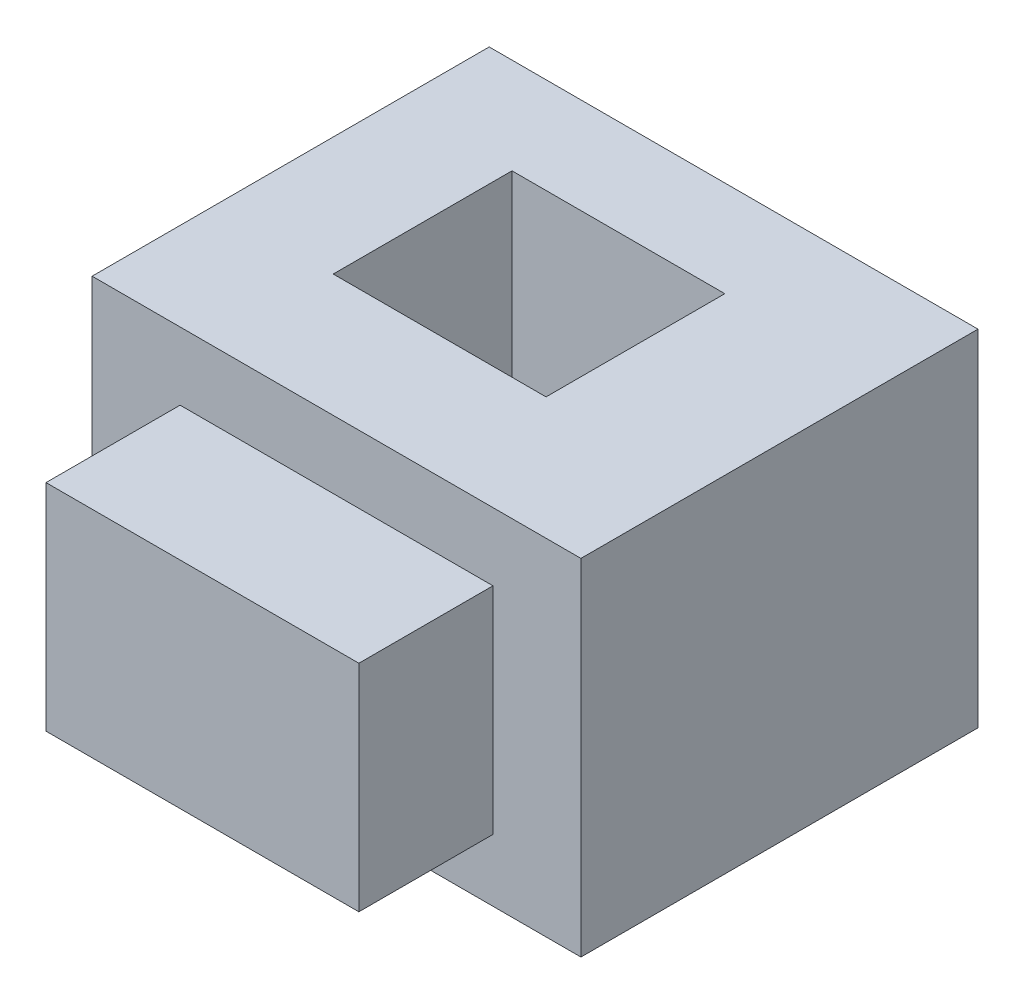
SolidWorks part; units mm, degrees
ref_plane "Front Plane" through (0, 0, 0) normal (0, 0, 1) x (1, 0, 0)
ref_plane "Top Plane" through (0, 0, 0) normal (0, 1, 0) x (1, 0, 0)
ref_plane "Right Plane" through (0, 0, 0) normal (1, 0, 0) x (0, 0, -1)
sketch "Sketch1" plane through (0, 0, 0) normal (0, 1, 0) x (1, 0, 0)
  line L1 (0, 0) -> (36.4531, 0)
  line L2 (0, 0) -> (0, 29.6127)
  line L3 (0, 29.6127) -> (36.4531, 29.6127)
  line L4 (36.4531, 0) -> (36.4531, 29.6127)
extrude "Boss-Extrude1" add sketch "Sketch1" along normal blind 25.7503
sketch "Sketch3" plane through (0, 0, 0) normal (0, 0, 1) x (1, 0, 0)
  line L1 (6.56, 20.699) -> (29.8931, 20.699)
  line L2 (6.56, 20.699) -> (6.56, 4.6431)
  line L3 (6.56, 4.6431) -> (29.8931, 4.6431)
  line L4 (29.8931, 20.699) -> (29.8931, 4.6431)
extrude "Boss-Extrude2" add sketch "Sketch3" along normal blind 10
sketch "Sketch4" plane through (0, 25.7503, 0) normal (0, 1, 0) x (1, 0, 0)
  line L1 (8.852, 22.4609) -> (24.7231, 22.4609)
  line L2 (8.852, 22.4609) -> (8.852, 9.1292)
  line L3 (8.852, 9.1292) -> (24.7231, 9.1292)
  line L4 (24.7231, 22.4609) -> (24.7231, 9.1292)
extrude "Cut-Extrude1" cut sketch "Sketch4" against normal through all
